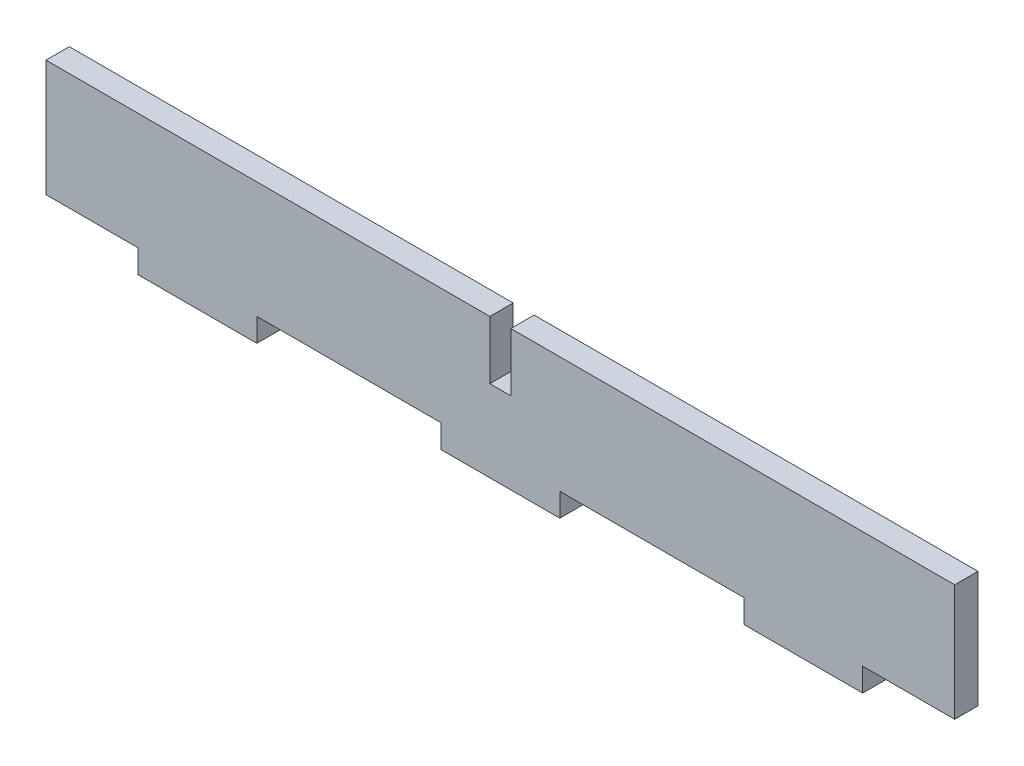
SolidWorks part; units mm, degrees
ref_plane "前基準面" through (0, 0, 0) normal (0, 0, 1) x (1, 0, 0)
ref_plane "上基準面" through (0, 0, 0) normal (0, 1, 0) x (1, 0, 0)
ref_plane "右基準面" through (0, 0, 0) normal (1, 0, 0) x (0, 0, -1)
sketch "草圖1" plane through (0, 0, 0) normal (0, 0, 1) x (1, 0, 0)
  line L0 (0, 0) -> (0, 19.9222) construction
  line L1 (-39, 2) -> (-31.1, 2)
  line L2 (-39, 2) -> (-39, 12)
  line L3 (-39, 12) -> (-0.9, 12)
  line L4 (39, 2) -> (39, 12)
  line L5 (-20.9, 2) -> (-5.1, 2)
  line L6 (31.1, 2) -> (39, 2)
  line L7 (-31.1, 2) -> (-31.1, 0)
  line L8 (-31.1, 0) -> (-20.9, 0)
  line L9 (-20.9, 2) -> (-20.9, 0)
  line L10 (0.9, 12) -> (39, 12)
  line L11 (20.9, 2) -> (20.9, 0)
  line L12 (20.9, 0) -> (31.1, 0)
  line L13 (31.1, 2) -> (31.1, 0)
  line L14 (0, 0) -> (-12.6558, 0) construction
  line L15 (-0.9, 12) -> (-0.9, 7)
  line L16 (-0.9, 7) -> (0.9, 7)
  line L17 (0.9, 12) -> (0.9, 7)
  line L18 (5.1, 2) -> (20.9, 2)
  line L19 (-26, 0) -> (-26, 36.2761) construction
  line L20 (-5.1, 2) -> (-5.1, 0)
  line L21 (-5.1, 0) -> (5.1, 0)
  line L22 (5.1, 2) -> (5.1, 0)
  line L23 (26, 0) -> (26, 34.9997) construction
  dimension "D1" = 78
  dimension "D2" = 10
  dimension "D3" = 2
  dimension "D4" = 26
  dimension "D5" = 10.2
  dimension "D6" = 2
  dimension "D7" = 1.8
  dimension "D8" = 5
  dimension "D9" = 10.2
  dimension "D10" = 2
extrude "填料-伸長1" add sketch "草圖1" along normal blind 2
